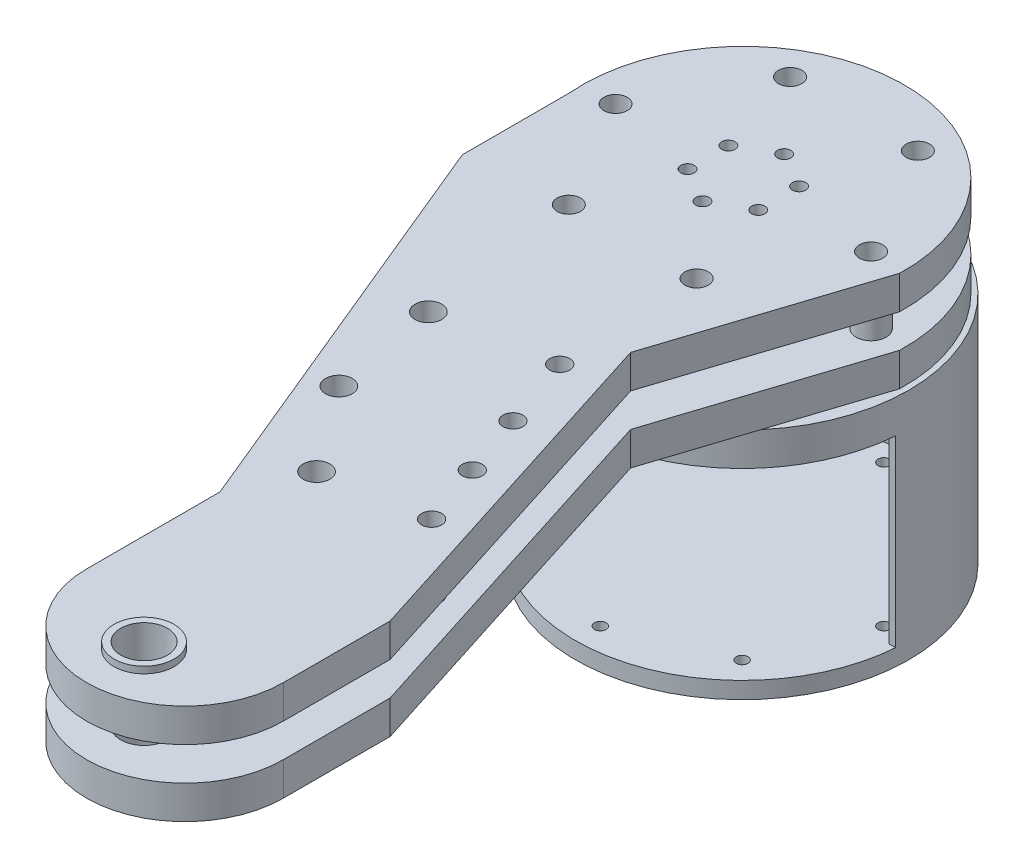
SolidWorks part; units mm, degrees
ref_plane "前视基准面" through (0, 0, 0) normal (0, 0, 1) x (1, 0, 0)
ref_plane "上视基准面" through (0, 0, 0) normal (0, 1, 0) x (1, 0, 0)
ref_plane "右视基准面" through (0, 0, 0) normal (1, 0, 0) x (0, 0, -1)
other "Configuration Table"
sketch "草图2" plane through (0, 0, 0) normal (0, 1, 0) x (1, 0, 0)
  line L0 (0, 0) -> (0, -32)
  line L1 (96.3007, 2.8025) -> (76.5236, -58.0652)
  line L2 (76.5236, -58.0652) -> (110.1947, -163.835)
  line L3 (0, -32) -> (51.1947, -155.835)
  line L4 (51.1947, -155.835) -> (51.1947, -195.835)
  line L5 (110.1947, -163.835) -> (110.1947, -195.835)
  line L6 (48.0699, 4.165) -> (48.0699, 16.4037) construction
  line L7 (48.0699, 4.165) -> (9.7734, 4.165) construction
  line L8 (80.6947, -195.835) -> (80.6947, -208.085)
  arc A0 (0, 0) -> (96.3007, 2.8025) centre (48.0699, 4.165) cw
  arc A2 (51.1947, -195.835) -> (110.1947, -195.835) centre (80.6947, -195.835) ccw
  circle A3 centre (36.244, -88.8006) radius 4
  circle A4 centre (46.7744, -114.2726) radius 4
  circle A5 centre (56.6866, -138.2492) radius 4
  circle A6 centre (87.4066, -130.743) radius 4
  circle A7 centre (77.6337, -104.4487) radius 4
  circle A8 centre (71.5008, -77.5769) radius 4
  dimension "D1" = 48.25
  dimension "D2" = 29.5
  dimension "D5" = 64
  dimension "D4" = 32
  dimension "D12" = 12.2387
  dimension "D3" = 200
  dimension "D6" = 134
  dimension "D7" = 111
  dimension "D8" = 40
  dimension "D9" = 32
  dimension "D10" = 4.802
  dimension "D11" = 18
  dimension "D13" = 38.2965
extrude "凸台-拉伸4" add sketch "草图2" along normal blind 10 contours L0 L3 L4 A2 L5 L2 L1 A0
sketch "草图5" plane through (0, 10, 0) normal (0, 1, 0) x (1, 0, 0)
  circle A0 centre (48.0699, 16.4037) radius 2
  circle A1 centre (9.7734, 4.165) radius 4
extrude "切除-拉伸3" cut sketch "草图5" against normal through all contours A0
pattern_circular "阵列(圆周)1" count 6 over 360 about axis through (48.0699, 10, -4.165) along (0, -1, 0) of "切除-拉伸3" reverse direction yes
sketch "草图6" plane through (0, 10, 0) normal (0, 1, 0) x (1, 0, 0)
  circle A0 centre (9.7734, 4.165) radius 3.5
extrude "切除-拉伸4" cut sketch "草图6" against normal through all
pattern_circular "阵列(圆周)2" count 6 over 360 about axis through (48.0699, 10, -4.165) along (0, -1, 0) of "切除-拉伸4" reverse direction yes
sketch "草图7" plane through (0, 10, 0) normal (0, 1, 0) x (1, 0, 0)
  circle A0 centre (80.6947, -208.085) radius 7
extrude "切除-拉伸6" cut sketch "草图7" against normal through all contours A0
ref_plane "基准面1" through (0, -5, 0) normal (0, 1, 0) x (1, 0, 0)
mirror "镜向6" about plane through (0, -5, 0) normal (0, 1, 0) of bodies 116
sketch "草图11" plane through (0, -5, 0) normal (0, 1, 0) x (1, 0, 0)
  circle A0 centre (9.7734, 4.165) radius 4.5
extrude "凸台-拉伸5" add sketch "草图11" along normal mid plane 20
pattern_circular "阵列(圆周)3" count 6 over 360 about axis through (48.0699, -20, -4.165) along (0, 1, 0) of "凸台-拉伸5" reverse direction yes
sketch "草图15" plane through (0, -10, 0) normal (0, 1, 0) x (1, 0, 0)
  circle A0 centre (40.2578, -76.1154) radius 10
  circle A1 centre (59.7423, -134.7943) radius 10
extrude "凸台-拉伸6" add sketch "草图15" along normal blind 10
ref_plane "基准面2" through (0, -20, 0) normal (0, -1, 0) x (-1, 0, 0)
sketch "草图26" plane through (0, -20, 0) normal (0, -1, 0) x (-1, 0, 0)
  circle A0 centre (-48.0342, 3.8371) radius 50
  circle A1 centre (-48.0699, 16.4037) radius 2
  circle A2 centre (-37.4709, 10.2844) radius 2
  circle A3 centre (-37.4709, -1.9543) radius 2
  circle A4 centre (-48.0699, -8.0737) radius 2
  circle A5 centre (-58.6689, -1.9543) radius 2
  circle A6 centre (-58.6689, 10.2844) radius 2
extrude "凸台-拉伸10" add sketch "草图26" along normal blind 5 contours A0
extrude "切除-拉伸14" cut sketch "草图26<5>" along normal blind 5 flip side to cut
sketch "草图26<5>" plane through (0, -20, 0) normal (0, -1, 0) x (-1, 0, 0) same geometry as "草图26"
sketch "草图27" plane through (0, -25, 0) normal (0, -1, 0) x (1, 0, 0)
  circle A0 centre (48.0342, -3.8371) radius 50
extrude "凸台-拉伸11" add sketch "草图27" along normal blind 65
sketch "草图28" plane through (0, -90, 0) normal (0, -1, 0) x (1, 0, 0)
  line L2 (-1.8183, 0) -> (97.8868, 0)
  circle A0 centre (48.0342, -3.8371) radius 50 construction
  arc A1 (-1.8183, 0) -> (97.8868, 0) centre (48.0342, -3.8371) cw
sketch "草图30" plane through (0, -90, 0) normal (0, -1, 0) x (1, 0, 0)
  line L1 (0, 0) -> (95.845, 0)
  arc A1 (0, 0) -> (95.845, 0) centre (47.9225, -3.9272) ccw
extrude "切除-拉伸16" cut sketch "草图30" against normal blind 55 from offset 5 offset against normal yes
extrude "切除-拉伸18" cut sketch "草图28" against normal blind 55 from offset 5 offset against normal yes
ref_plane "基准面3" through (0, -90, 0) normal (0, -1, 0) x (-1, 0, 0)
sketch "草图31" plane through (0, -90, 0) normal (0, -1, 0) x (-1, 0, 0)
  circle A0 centre (-48.0342, 46.3371) radius 1.75
extrude "切除-拉伸19" cut sketch "草图31" against normal blind 5
pattern_circular "阵列(圆周)4" count 8 over 360 about axis through (48.0342, -25, -3.8371) along (0, 1, 0) of "切除-拉伸19"
sketch "草图32" plane through (0, -20, 0) normal (0, -1, 0) x (1, 0, 0)
  circle A1 centre (80.6947, 208.085) radius 7
  circle A2 centre (80.6947, 208.085) radius 9
extrude "凸台-拉伸12" add sketch "草图32" along normal blind 2
sketch "草图33" plane through (0, 10, 0) normal (0, 1, 0) x (1, 0, 0)
  circle A0 centre (68.9933, -71.7932) radius 3
  circle A1 centre (76.6582, -93.4784) radius 3
  circle A2 centre (83.3234, -112.3351) radius 3
  circle A3 centre (89.9886, -131.1918) radius 3
  dimension "D1" = 20
  dimension "D2" = 20
extrude "切除-拉伸20" cut sketch "草图33" against normal through all
sketch "草图34" plane through (0, 10, 0) normal (0, 1, 0) x (1, 0, 0)
  circle A0 centre (35.6816, -77.8467) radius 4
  circle A1 centre (41.5381, -110.5399) radius 4
  circle A2 centre (60.3833, -136.0765) radius 4
extrude "切除-拉伸21" cut sketch "草图34" against normal blind 10
ref_plane "基准面4" through (0, -5, 0) normal (0, 1, 0) x (1, 0, 0)
mirror "镜向7" about plane through (0, -5, 0) normal (0, 1, 0) of "切除-拉伸21"
mirror "镜向8" about plane through (0, -5, 0) normal (0, 1, 0) of "凸台-拉伸12"
